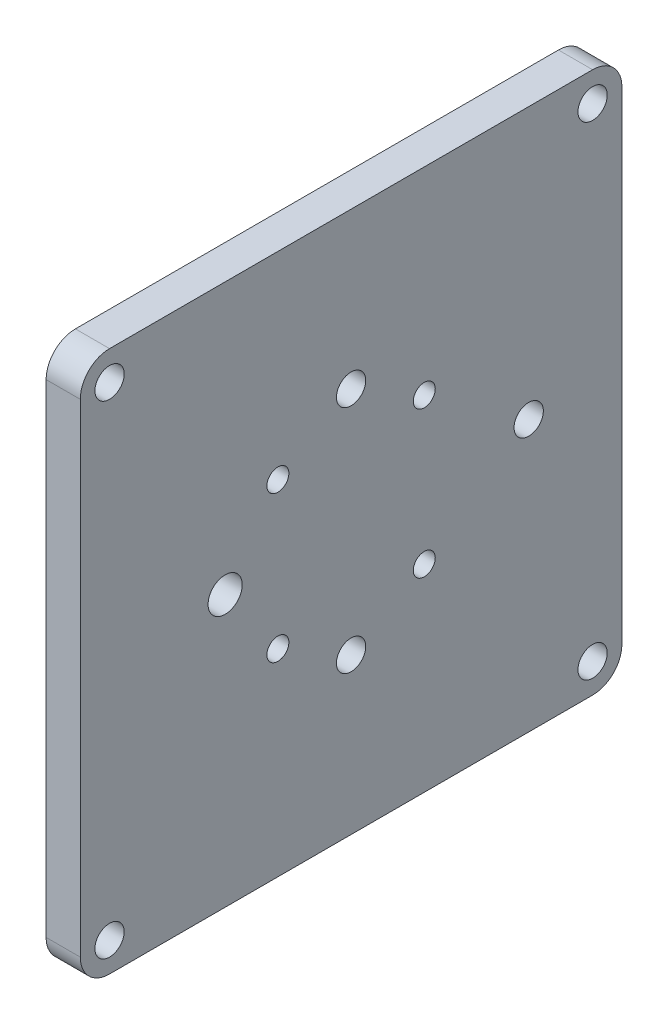
SolidWorks part; units mm, degrees
material "ABS"
ref_plane "Front Plane" through (0, 0, 0) normal (1, 0, 0) x (0, 1, 0)
ref_plane "Top Plane" through (0, 0, 0) normal (0, 0, 1) x (0, 1, 0)
ref_plane "Right Plane" through (0, 0, 0) normal (0, 1, 0) x (-1, 0, 0)
sketch "Sketch1" plane through (0, 0, 0) normal (1, 0, 0) x (0, 1, 0)
  line L0 (-23.6, 0) -> (23.6, 0) construction
  line L1 (0, 0) -> (0, 25.8061) construction
  line L2 (0, 25.8061) -> (0, -36.4) construction
  circle A0 centre (-23.6, 0) radius 3
  circle A1 centre (23.6, 0) radius 3
  circle A2 centre (0, 25.8061) radius 3.5
  circle A3 centre (0, -36.4) radius 3
  circle A4 centre (0, 25.8061) radius 7.5
  circle A5 centre (-23.6, 0) radius 7
  circle A6 centre (0, -36.4) radius 7
  circle A7 centre (23.6, 0) radius 7
  point P18 (0, 25.8061)
  dimension "D2" = 25.8061
  dimension "D3" = 6
  dimension "D4" = 6
  dimension "D5" = 7
  dimension "D7" = 6
  dimension "D1" = 47.2
  dimension "D6" = 62.2061
  dimension "D8" = 4
extrude "Boss-Extrude1" add sketch "Sketch1" along normal blind 13.6
sketch "Sketch2" plane through (13.6, 0, 0) normal (1, 0, 0) x (0, 1, 0)
  line L0 (-7.1532, 23.5517) -> (-23.6, 7)
  line L1 (-23.6, -7) -> (-7, -36.4)
  line L2 (7, -36.4) -> (23.6, -7)
  line L3 (23.6, 7) -> (7.1532, 23.5517)
  circle A2 centre (0, 25.8061) radius 7.5 construction
  circle A3 centre (-23.6, 0) radius 7 construction
  circle A4 centre (0, -36.4) radius 7 construction
  circle A5 centre (23.6, 0) radius 7 construction
  arc A6 (23.6, 7) -> (23.6, -7) centre (23.6, 0) ccw
  arc A7 (7, -36.4) -> (-7, -36.4) centre (0, -36.4) ccw
  arc A8 (-23.6, -7) -> (-23.6, 7) centre (-23.6, 0) ccw
  arc A9 (-7.1532, 23.5517) -> (7.1532, 23.5517) centre (0, 25.8061) ccw
extrude "Boss-Extrude2" add sketch "Sketch2" against normal up to surface (13.6 mm away) up to face at (0, -23.6, -7)
sketch "Sketch3" plane through (13.6, 0, 0) normal (1, 0, 0) x (0, 1, 0)
  circle A0 centre (15, 15) radius 2.25
  circle A1 centre (15, -15) radius 2.25
  circle A2 centre (-15, -15) radius 2.25
  circle A3 centre (-15, 15) radius 2.25
  point P0 (0, 0)
  dimension "D3" = 4.5
  dimension "D4" = 4.5
  dimension "D5" = 4.5
  dimension "D6" = 4.5
  dimension "D1" = 30
  dimension "D2" = 30
extrude "Cut-Extrude1" cut sketch "Sketch3" against normal blind 27.6
sketch "Sketch4" plane through (13.6, 0, 0) normal (1, 0, 0) x (0, 1, 0)
  circle A0 centre (-15, 15) radius 5
  circle A1 centre (15, 15) radius 5
  circle A2 centre (15, -15) radius 5
  circle A3 centre (-15, -15) radius 5
  circle A4 centre (-15, 15) radius 2.25
  circle A5 centre (15, 15) radius 2.25
  circle A6 centre (15, -15) radius 2.25
  circle A7 centre (-15, -15) radius 2.25
  dimension "D1" = 10
  dimension "D2" = 10
  dimension "D3" = 10
  dimension "D4" = 10
extrude "Boss-Extrude3" add sketch "Sketch4" against normal up to surface (13.6 mm away) up to face at (0, -15, -17.25)
sketch "Sketch5" plane through (0, 0, 0) normal (1, 0, 0) x (0, 1, 0)
  line L0 (-9.3322, -12.6384) -> (0, -27.2452)
  line L1 (-9.3322, 12.6384) -> (9.3322, 12.6384)
  line L2 (-9.3322, 12.6384) -> (-9.3322, -12.6384)
  line L4 (9.3322, 12.6384) -> (9.3322, -12.6384)
  line L7 (9.3322, -12.6384) -> (0, -27.2452)
  point P0 (0, 0)
extrude "Cut-Extrude2" cut sketch "Sketch5" along normal blind 32.6
fillet "Fillet1" radius 4 5 edges at (6.8, 0, -27.2452) (6.8, 9.3322, -12.6384) (6.8, -9.3322, -12.6384) (6.8, 9.3322, 12.6384) (6.8, -9.3322, 12.6384)
sketch "Sketch6" plane through (0, 0, 0) normal (-1, 0, 0) x (0, -1, 0)
  line L0 (18.5355, 18.5355) -> (49.4975, 49.4975) construction
  line L1 (18.5355, -18.5355) -> (49.4975, -49.4975) construction
  line L2 (-51.756, 47.5229) -> (-52.1138, 46.8812)
  line L3 (-46.8812, 52.1138) -> (-47.3762, 51.6188)
  line L4 (46.8812, 52.1138) -> (47.3762, 51.6188)
  line L5 (14.7617, 19.9943) -> (46.8812, 52.1138)
  line L6 (52.1138, 46.8812) -> (51.6188, 47.3762)
  line L7 (46.8812, -52.1138) -> (47.3762, -51.6188)
  line L8 (52.1138, -46.8812) -> (51.6188, -47.3762)
  line L9 (-52.1138, -46.8812) -> (-51.6188, -47.3762)
  line L10 (-46.8812, -52.1138) -> (-47.3762, -51.6188)
  line L11 (-15.7213, -20.9539) -> (-46.8812, -52.1138)
  line L12 (-19.9943, 14.7617) -> (-52.1138, 46.8812)
  line L14 (23.6, 7) -> (18.8366, 11.7937)
  line L15 (11.8182, 18.8569) -> (7.1532, 23.5517)
  line L16 (-7.1532, 23.5517) -> (-11.8182, 18.8569)
  line L17 (-18.8366, 11.7937) -> (-23.6, 7)
  line L18 (-23.6, -7) -> (-19.8245, -13.6868)
  line L19 (-16.3675, -19.8094) -> (-7, -36.4)
  line L20 (7, -36.4) -> (16.3675, -19.8094)
  line L21 (19.8245, -13.6868) -> (23.6, -7)
  line L27 (-16.3675, -19.8094) -> (-15.7213, -20.9539)
  line L28 (15.7213, -20.9539) -> (16.3675, -19.8094)
  line L30 (-18.5355, 18.5355) -> (-49.4975, 49.4975) construction
  line L32 (-2.6163, 2.6163) -> (46.8812, 52.1138) construction
  line L33 (0, 0) -> (49.4975, 49.4975) construction
  line L36 (15.7213, -20.9539) -> (46.8812, -52.1138)
  line L38 (-18.5355, -18.5355) -> (-49.4975, -49.4975) construction
  line L40 (-19.9943, -14.7617) -> (-52.1138, -46.8812)
  line L42 (-14.7617, 19.9943) -> (-46.8812, 52.1138)
  line L44 (19.9943, 14.7617) -> (52.1138, 46.8812)
  line L46 (19.9943, -14.7617) -> (52.1138, -46.8812)
  line L48 (0, 0) -> (-2.6163, 2.6163) construction
  line L49 (0, 0) -> (-2.6163, -2.6163) construction
  arc A0 (-51.756, 47.5229) -> (-47.3762, 51.6188) centre (-49.4975, 49.4975) ccw
  arc A1 (47.3762, 51.6188) -> (51.6188, 47.3762) centre (49.4975, 49.4975) ccw
  arc A2 (51.6188, -47.3762) -> (47.3762, -51.6188) centre (49.4975, -49.4975) ccw
  arc A3 (-47.3762, -51.6188) -> (-51.6188, -47.3762) centre (-49.4975, -49.4975) ccw
  arc A8 (18.8366, 11.7937) -> (11.8182, 18.8569) centre (15, 15) ccw
  arc A9 (7.1532, 23.5517) -> (-7.1532, 23.5517) centre (0, 25.8061) ccw
  arc A10 (-11.8182, 18.8569) -> (-18.8366, 11.7937) centre (-15, 15) ccw
  arc A11 (-23.6, 7) -> (-23.6, -7) centre (-23.6, 0) ccw
  arc A12 (-19.8245, -13.6868) -> (-16.3675, -19.8094) centre (-15, -15) ccw
  arc A13 (-7, -36.4) -> (7, -36.4) centre (0, -36.4) ccw
  arc A14 (16.3675, -19.8094) -> (19.8245, -13.6868) centre (15, -15) ccw
  arc A15 (23.6, -7) -> (23.6, 7) centre (23.6, 0) ccw
  arc A16 (19.9943, 14.7617) -> (14.7617, 19.9943) centre (15, 15) ccw
  arc A18 (-14.7617, 19.9943) -> (-19.9943, 14.7617) centre (-15, 15) ccw
  arc A20 (-19.9943, -14.7617) -> (-16.3675, -19.8094) centre (-15, -15) ccw
  arc A22 (16.3675, -19.8094) -> (19.9943, -14.7617) centre (15, -15) ccw
  point P6 (67.0007, 67.0007)
  dimension "D3" = 6
  dimension "D6" = 6
  dimension "D7" = 6
  dimension "D8" = 6
  dimension "D1" = 70
  dimension "D4" = 3.7
  dimension "D5" = 0
  dimension "D2" = 4
extrude "Boss-Extrude4" add sketch "Sketch6" against normal blind 3
fillet "Fillet2" radius 4 4 edges at (3, 19.0605, -17.9176) (3, 18.5355, 18.5355) (3, -19.0605, -17.9176) (3, -18.5355, 18.5355)
sketch "Sketch7" plane through (13.6, 0, 0) normal (1, 0, 0) x (0, 1, 0)
  line L8 (-18.8366, 11.7937) -> (-23.6, 7)
  line L9 (-23.6, -7) -> (-19.8245, -13.6868)
  line L10 (-16.3675, -19.8094) -> (-7, -36.4)
  line L11 (7, -36.4) -> (16.3675, -19.8094)
  line L12 (19.8245, -13.6868) -> (23.6, -7)
  line L13 (23.6, 7) -> (18.8366, 11.7937)
  line L14 (11.8182, 18.8569) -> (7.1532, 23.5517)
  line L15 (-7.1532, 23.5517) -> (-11.8182, 18.8569)
  line L16 (-18.8366, 11.7937) -> (-23.6, 7)
  line L17 (-23.6, -7) -> (-19.8245, -13.6868)
  line L18 (-16.3675, -19.8094) -> (-7, -36.4)
  line L19 (7, -36.4) -> (16.3675, -19.8094)
  line L20 (19.8245, -13.6868) -> (23.6, -7)
  line L21 (23.6, 7) -> (18.8366, 11.7937)
  line L22 (11.8182, 18.8569) -> (7.1532, 23.5517)
  line L23 (-7.1532, 23.5517) -> (-11.8182, 18.8569)
  arc A8 (-11.8182, 18.8569) -> (-18.8366, 11.7937) centre (-15, 15) ccw
  arc A9 (-23.6, 7) -> (-23.6, -7) centre (-23.6, 0) ccw
  arc A10 (-19.8245, -13.6868) -> (-16.3675, -19.8094) centre (-15, -15) ccw
  arc A11 (-7, -36.4) -> (7, -36.4) centre (0, -36.4) ccw
  arc A12 (16.3675, -19.8094) -> (19.8245, -13.6868) centre (15, -15) ccw
  arc A13 (23.6, -7) -> (23.6, 7) centre (23.6, 0) ccw
  arc A14 (18.8366, 11.7937) -> (11.8182, 18.8569) centre (15, 15) ccw
  arc A15 (7.1532, 23.5517) -> (-7.1532, 23.5517) centre (0, 25.8061) ccw
  arc A16 (-11.8182, 18.8569) -> (-18.8366, 11.7937) centre (-15, 15) ccw
  arc A17 (-23.6, 7) -> (-23.6, -7) centre (-23.6, 0) ccw
  arc A18 (-19.8245, -13.6868) -> (-16.3675, -19.8094) centre (-15, -15) ccw
  arc A19 (-7, -36.4) -> (7, -36.4) centre (0, -36.4) ccw
  arc A20 (16.3675, -19.8094) -> (19.8245, -13.6868) centre (15, -15) ccw
  arc A21 (23.6, -7) -> (23.6, 7) centre (23.6, 0) ccw
  arc A22 (18.8366, 11.7937) -> (11.8182, 18.8569) centre (15, 15) ccw
  arc A23 (7.1532, 23.5517) -> (-7.1532, 23.5517) centre (0, 25.8061) ccw
  dimension "D1" = 0
extrude "Cut-Extrude4" cut sketch "Sketch7" against normal up to vertex (6.6 mm away) up to point (7, -16.3675, -19.8094)
sketch "Sketch9" plane through (3, 0, 0) normal (1, 0, 0) x (0, 1, 0)
  circle A0 centre (-49.4975, 49.4975) radius 3
  circle A1 centre (-49.4975, 49.4975) radius 6
  circle A2 centre (49.4975, 49.4975) radius 6
  circle A3 centre (49.4975, 49.4975) radius 3
  circle A4 centre (49.4975, -49.4975) radius 6
  circle A5 centre (49.4975, -49.4975) radius 3
  circle A6 centre (-49.4975, -49.4975) radius 6
  circle A7 centre (-49.4975, -49.4975) radius 3
  dimension "D1" = 3
  dimension "D2" = 4
extrude "Boss-Extrude5" add sketch "Sketch9" against normal up to surface (3 mm away) up to face at (0, 0.0037, 0.2465)
sketch "Sketch10" plane through (0, 0, 0) normal (-1, 0, 0) x (0, -1, 0)
  line L0 (-49.4975, 55.4975) -> (49.4975, 55.4975)
  line L1 (-55.4975, 49.4975) -> (-55.4975, -49.4975)
  line L2 (-49.4975, -55.4975) -> (49.4975, -55.4975)
  line L3 (55.4975, -49.4975) -> (55.4975, 49.4975)
  line L16 (19.9943, 14.7617) -> (48.7739, 43.5413)
  line L17 (43.5413, 48.7739) -> (14.7617, 19.9943)
  line L18 (11.8182, 18.8569) -> (7.1532, 23.5517)
  line L19 (-7.1532, 23.5517) -> (-11.8182, 18.8569)
  line L20 (-14.7617, 19.9943) -> (-43.5413, 48.7739)
  line L21 (-48.7739, 43.5413) -> (-19.9943, 14.7617)
  line L22 (-18.8366, 11.7937) -> (-23.6, 7)
  line L23 (-23.6, -7) -> (-19.8245, -13.6868)
  line L24 (-19.9943, -14.7617) -> (-48.7739, -43.5413)
  line L25 (-43.5413, -48.7739) -> (-15.7213, -20.9539)
  line L26 (-15.7213, -20.9539) -> (-7, -36.4)
  line L27 (7, -36.4) -> (15.7213, -20.9539)
  line L28 (15.7213, -20.9539) -> (43.5413, -48.7739)
  line L29 (48.7739, -43.5413) -> (19.9943, -14.7617)
  line L30 (19.8245, -13.6868) -> (23.6, -7)
  line L31 (23.6, 7) -> (18.8366, 11.7937)
  line L32 (19.9943, 14.7617) -> (48.7739, 43.5413)
  line L33 (43.5413, 48.7739) -> (14.7617, 19.9943)
  line L34 (11.8182, 18.8569) -> (7.1532, 23.5517)
  line L35 (-7.1532, 23.5517) -> (-11.8182, 18.8569)
  line L36 (-14.7617, 19.9943) -> (-43.5413, 48.7739)
  line L37 (-48.7739, 43.5413) -> (-19.9943, 14.7617)
  line L38 (-18.8366, 11.7937) -> (-23.6, 7)
  line L39 (-23.6, -7) -> (-19.8245, -13.6868)
  line L40 (-19.9943, -14.7617) -> (-48.7739, -43.5413)
  line L41 (-43.5413, -48.7739) -> (-15.7213, -20.9539)
  line L42 (-15.7213, -20.9539) -> (-7, -36.4)
  line L43 (7, -36.4) -> (15.7213, -20.9539)
  line L44 (15.7213, -20.9539) -> (43.5413, -48.7739)
  line L45 (48.7739, -43.5413) -> (19.9943, -14.7617)
  line L46 (19.8245, -13.6868) -> (23.6, -7)
  line L47 (23.6, 7) -> (18.8366, 11.7937)
  circle A0 centre (49.4975, -49.4975) radius 3 construction
  circle A1 centre (-49.4975, 49.4975) radius 3 construction
  circle A2 centre (49.4975, 49.4975) radius 3 construction
  circle A3 centre (-15, -15) radius 2.25 construction
  circle A4 centre (0, -36.4) radius 3 construction
  circle A5 centre (15, -15) radius 2.25 construction
  circle A6 centre (23.6, 0) radius 3 construction
  circle A7 centre (15, 15) radius 2.25 construction
  circle A8 centre (0, 25.8061) radius 3.5 construction
  circle A9 centre (-15, 15) radius 2.25 construction
  circle A10 centre (-23.6, 0) radius 3 construction
  circle A11 centre (-49.4975, -49.4975) radius 3 construction
  circle A12 centre (49.4975, -49.4975) radius 3
  circle A13 centre (-49.4975, 49.4975) radius 3
  arc A14 (48.7739, 43.5413) -> (43.5413, 48.7739) centre (49.4975, 49.4975) ccw
  arc A15 (14.7617, 19.9943) -> (11.8182, 18.8569) centre (15, 15) ccw
  arc A16 (7.1532, 23.5517) -> (-7.1532, 23.5517) centre (0, 25.8061) ccw
  arc A17 (-11.8182, 18.8569) -> (-14.7617, 19.9943) centre (-15, 15) ccw
  arc A18 (-43.5413, 48.7739) -> (-48.7739, 43.5413) centre (-49.4975, 49.4975) ccw
  arc A19 (-19.9943, 14.7617) -> (-18.8366, 11.7937) centre (-15, 15) ccw
  arc A20 (-23.6, 7) -> (-23.6, -7) centre (-23.6, 0) ccw
  arc A21 (-19.8245, -13.6868) -> (-19.9943, -14.7617) centre (-15, -15) ccw
  arc A22 (-48.7739, -43.5413) -> (-43.5413, -48.7739) centre (-49.4975, -49.4975) ccw
  arc A23 (-7, -36.4) -> (7, -36.4) centre (0, -36.4) ccw
  arc A24 (43.5413, -48.7739) -> (48.7739, -43.5413) centre (49.4975, -49.4975) ccw
  arc A25 (19.9943, -14.7617) -> (19.8245, -13.6868) centre (15, -15) ccw
  arc A26 (23.6, -7) -> (23.6, 7) centre (23.6, 0) ccw
  arc A27 (18.8366, 11.7937) -> (19.9943, 14.7617) centre (15, 15) ccw
  arc A28 (48.7739, 43.5413) -> (55.4975, 49.4975) centre (49.4975, 49.4975) ccw
  arc A29 (14.7617, 19.9943) -> (11.8182, 18.8569) centre (15, 15) ccw
  arc A30 (7.1532, 23.5517) -> (-7.1532, 23.5517) centre (0, 25.8061) ccw
  arc A31 (-11.8182, 18.8569) -> (-14.7617, 19.9943) centre (-15, 15) ccw
  arc A32 (-43.5413, 48.7739) -> (-49.4975, 55.4975) centre (-49.4975, 49.4975) ccw
  arc A33 (-19.9943, 14.7617) -> (-18.8366, 11.7937) centre (-15, 15) ccw
  arc A34 (-23.6, 7) -> (-23.6, -7) centre (-23.6, 0) ccw
  arc A35 (-19.8245, -13.6868) -> (-19.9943, -14.7617) centre (-15, -15) ccw
  arc A36 (-48.7739, -43.5413) -> (-55.4975, -49.4975) centre (-49.4975, -49.4975) ccw
  arc A37 (-7, -36.4) -> (7, -36.4) centre (0, -36.4) ccw
  arc A38 (43.5413, -48.7739) -> (49.4975, -55.4975) centre (49.4975, -49.4975) ccw
  arc A39 (19.9943, -14.7617) -> (19.8245, -13.6868) centre (15, -15) ccw
  arc A40 (23.6, -7) -> (23.6, 7) centre (23.6, 0) ccw
  arc A41 (18.8366, 11.7937) -> (19.9943, 14.7617) centre (15, 15) ccw
  circle A42 centre (49.4975, 49.4975) radius 3
  circle A43 centre (-15, -15) radius 2.25
  circle A44 centre (0, -36.4) radius 3
  circle A45 centre (15, -15) radius 2.25
  circle A46 centre (23.6, 0) radius 3
  circle A47 centre (15, 15) radius 2.25
  circle A48 centre (0, 25.8061) radius 3.5
  circle A49 centre (-15, 15) radius 2.25
  circle A50 centre (-23.6, 0) radius 3
  circle A51 centre (-49.4975, -49.4975) radius 3
  arc A52 (-55.4975, 49.4975) -> (-48.7739, 43.5413) centre (-49.4975, 49.4975) ccw
  arc A53 (49.4975, 55.4975) -> (43.5413, 48.7739) centre (49.4975, 49.4975) ccw
  arc A54 (55.4975, -49.4975) -> (48.7739, -43.5413) centre (49.4975, -49.4975) ccw
  arc A55 (-49.4975, -55.4975) -> (-43.5413, -48.7739) centre (-49.4975, -49.4975) ccw
  dimension "D1" = 0
extrude "Boss-Extrude6" add sketch "Sketch10" against normal up to surface (7 mm away) up to face at (7, 0, 22.3061)
sketch "Sketch12" plane through (3, 0, 0) normal (1, 0, 0) x (0, 1, 0)
  line L0 (49.4975, -55.4975) -> (-49.4975, -55.4975) construction
  line L1 (55.4975, 49.4975) -> (55.4975, -49.4975) construction
  line L2 (-49.4975, 55.4975) -> (49.4975, 55.4975) construction
  line L3 (-55.4975, -49.4975) -> (-55.4975, 49.4975) construction
  line L4 (49.4975, -55.4975) -> (-49.4975, -55.4975)
  line L5 (55.4975, 49.4975) -> (55.4975, -49.4975)
  line L6 (-49.4975, 55.4975) -> (49.4975, 55.4975)
  line L7 (-55.4975, -49.4975) -> (-55.4975, 49.4975)
  circle A0 centre (-49.4975, -49.4975) radius 6 construction
  circle A1 centre (49.4975, -49.4975) radius 6 construction
  circle A2 centre (49.4975, 49.4975) radius 6 construction
  circle A3 centre (-49.4975, 49.4975) radius 6 construction
  arc A4 (-55.4975, -49.4975) -> (-49.4975, -55.4975) centre (-49.4975, -49.4975) ccw
  arc A5 (49.4975, -55.4975) -> (55.4975, -49.4975) centre (49.4975, -49.4975) ccw
  arc A6 (55.4975, 49.4975) -> (49.4975, 55.4975) centre (49.4975, 49.4975) ccw
  arc A7 (-49.4975, 55.4975) -> (-55.4975, 49.4975) centre (-49.4975, 49.4975) ccw
extrude "Boss-Extrude7" add sketch "Sketch12" along normal up to surface (4 mm away) up to face at (7, 0, -1.5572)
sketch "Sketch11" plane through (0, 0, 0) normal (-1, 0, 0) x (0, -1, 0)
  circle A0 centre (49.4975, 49.4975) radius 3 construction
  circle A1 centre (-49.4975, 49.4975) radius 3 construction
  circle A2 centre (-49.4975, -49.4975) radius 3 construction
  circle A3 centre (49.4975, -49.4975) radius 3 construction
  circle A4 centre (0, -36.4) radius 3 construction
  circle A5 centre (-23.6, 0) radius 3 construction
  circle A6 centre (-15, -15) radius 2.25 construction
  circle A7 centre (15, 15) radius 2.25 construction
  circle A8 centre (-15, 15) radius 2.25 construction
  circle A9 centre (0, 25.8061) radius 3.5 construction
  circle A10 centre (23.6, 0) radius 3 construction
  circle A11 centre (15, -15) radius 2.25 construction
  circle A12 centre (49.4975, 49.4975) radius 3
  circle A13 centre (-49.4975, 49.4975) radius 3
  circle A14 centre (-49.4975, -49.4975) radius 3
  circle A15 centre (49.4975, -49.4975) radius 3
  circle A16 centre (0, -36.4) radius 3
  circle A17 centre (-23.6, 0) radius 3
  circle A18 centre (-15, -15) radius 2.25
  circle A19 centre (15, 15) radius 2.25
  circle A20 centre (-15, 15) radius 2.25
  circle A21 centre (0, 25.8061) radius 3.5
  circle A22 centre (23.6, 0) radius 3
  circle A23 centre (15, -15) radius 2.25
extrude "Cut-Extrude5" cut sketch "Sketch11" against normal blind 57 and the other way blind 196
sketch "Sketch13" plane through (3, 0, 0) normal (-1, 0, 0) x (0, -1, 0)
  line L5 (-8.703, -13.6232) -> (-3.3708, -21.9692)
  line L6 (3.3708, -21.9692) -> (8.703, -13.6232)
  line L7 (9.3322, -11.4697) -> (9.3322, 8.6384)
  line L8 (5.3322, 12.6384) -> (-5.3322, 12.6384)
  line L9 (-9.3322, 8.6384) -> (-9.3322, -11.4697)
  line L10 (-8.703, -13.6232) -> (-3.3708, -21.9692)
  line L11 (3.3708, -21.9692) -> (8.703, -13.6232)
  line L12 (9.3322, -11.4697) -> (9.3322, 8.6384)
  line L13 (5.3322, 12.6384) -> (-5.3322, 12.6384)
  line L14 (-9.3322, 8.6384) -> (-9.3322, -11.4697)
  arc A5 (-3.3708, -21.9692) -> (3.3708, -21.9692) centre (0, -19.8157) ccw
  arc A6 (8.703, -13.6232) -> (9.3322, -11.4697) centre (5.3322, -11.4697) ccw
  arc A7 (9.3322, 8.6384) -> (5.3322, 12.6384) centre (5.3322, 8.6384) ccw
  arc A8 (-5.3322, 12.6384) -> (-9.3322, 8.6384) centre (-5.3322, 8.6384) ccw
  arc A9 (-9.3322, -11.4697) -> (-8.703, -13.6232) centre (-5.3322, -11.4697) ccw
  arc A10 (-3.3708, -21.9692) -> (3.3708, -21.9692) centre (0, -19.8157) ccw
  arc A11 (8.703, -13.6232) -> (9.3322, -11.4697) centre (5.3322, -11.4697) ccw
  arc A12 (9.3322, 8.6384) -> (5.3322, 12.6384) centre (5.3322, 8.6384) ccw
  arc A13 (-5.3322, 12.6384) -> (-9.3322, 8.6384) centre (-5.3322, 8.6384) ccw
  arc A14 (-9.3322, -11.4697) -> (-8.703, -13.6232) centre (-5.3322, -11.4697) ccw
  dimension "D1" = 0
extrude "Boss-Extrude8" add sketch "Sketch13" along normal up to surface (3 mm away) up to face at (0, 15, 12.75)
